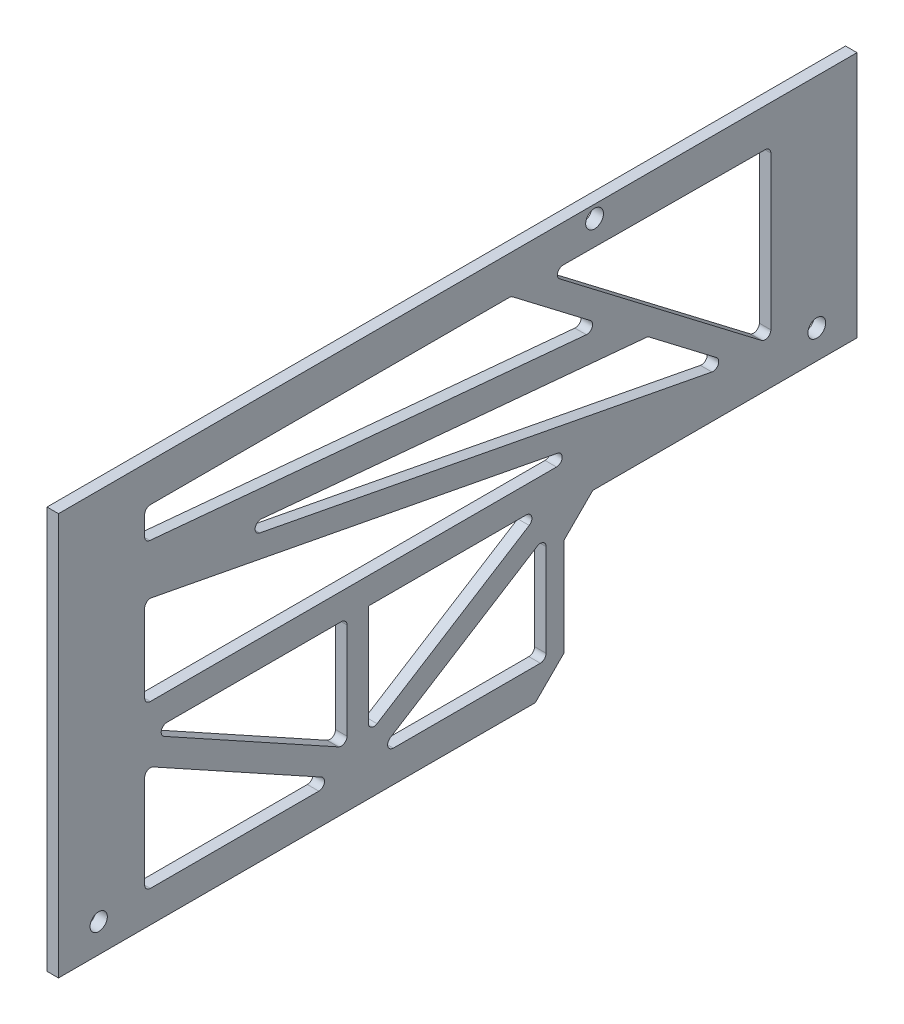
SolidWorks part; units mm, degrees
material "PE 低密度结膜"
ref_plane "前视基准面" through (0, 0, 0) normal (0, 0, 1) x (1, 0, 0)
ref_plane "上视基准面" through (0, 0, 0) normal (0, 1, 0) x (1, 0, 0)
ref_plane "右视基准面" through (0, 0, 0) normal (1, 0, 0) x (0, 0, -1)
sketch "草图2" plane through (0, 0, 0) normal (1, 0, 0) x (0, 0, -1)
  line L1 (0, 0) -> (139, 0)
  line L2 (0, 0) -> (0, 110)
  line L3 (0, 110) -> (139, 110)
  line L4 (139, 0) -> (139, 110)
  line L5 (139, 0) -> (88, 0)
  line L6 (139, 0) -> (139, 27)
  line L7 (139, 27) -> (88, 27)
  line L8 (88, 0) -> (88, 27)
  dimension "D1" = 139
  dimension "D2" = 110
  dimension "D3" = 51
  dimension "D4" = 27
extrude "凸台-拉伸1" add sketch "草图2" along normal blind 2 contours L1 L8 L7 L4 L3 L2 region at (0, 59.1073, -65.1452)
sketch "草图3" plane through (0, 110, 0) normal (0, 1, 0) x (1, 0, 0)
  line L1 (0, 139) -> (2, 139)
  line L2 (0, 139) -> (0, 0)
  line L3 (0, 0) -> (2, 0)
  line L4 (2, 139) -> (2, 0)
extrude "切除-拉伸1" cut sketch "草图3" against normal blind 40
sketch "草图4" plane through (-10, 0, 0) normal (-1, 0, 0) x (0, 0, 1)
  circle A0 centre (-7, 5) radius 1.5
  circle A1 centre (-132, 30) radius 1.5
  circle A3 centre (-93.3167, 67.822) radius 1.55
  dimension "D1" = 3.1
extrude "切除-拉伸3" cut sketch "草图4" against normal blind 14
sketch "草图5" plane through (2, 0, 0) normal (1, 0, 0) x (0, 0, -1)
  circle A0 centre (132, 30) radius 1.5
extrude "凸台-拉伸2" add sketch "草图5" against normal up to surface (2 mm away) up to face at (0, 5, -8.5)
sketch "草图6" plane through (2, 0, 0) normal (1, 0, 0) x (0, 0, -1)
  line L1 (139, 27) -> (132, 27)
  line L2 (139, 27) -> (139, 32)
  line L3 (139, 32) -> (132, 32)
  line L4 (132, 27) -> (132, 32)
  circle A0 centre (132, 32) radius 1.55
  dimension "D3" = 3.1
  dimension "D1" = 5
  dimension "D2" = 7
extrude "切除-拉伸4" cut sketch "草图6" against normal blind 10 contours L3 A0 L4 | L4 A0 L3 region at (2, 32.2193, -131.7807) region at (2, 31.3422, -132.6578)
chamfer "Chamfer1" distance 5 angle 45 2 edges at (1, 0, -88) (1, 27, -88)
sketch "Sketch1" plane through (0, 0, 0) normal (-1, 0, 0) x (0, 0, 1)
  line L0 (-93.3991, 57.0699) -> (-124, 33.6882)
  line L1 (-124, 33.6882) -> (-124, 54.2625)
  line L3 (-102.609, 45.3791) -> (-117.9095, 33.6882)
  line L4 (-117.9095, 33.6882) -> (-15, 53.4166)
  line L5 (-15, 53.4166) -> (-102.609, 45.3791)
  line L6 (-15, 49.4486) -> (-15, 33.6882)
  line L7 (-15, 33.6882) -> (-97.2112, 33.6882)
  line L8 (-97.2112, 33.6882) -> (-15, 49.4486)
  line L9 (-15, 29.1023) -> (-50.2247, 29.1023)
  line L10 (-50.2247, 29.1023) -> (-50.2247, 9.6509)
  line L11 (-50.2247, 9.6509) -> (-15, 29.1023)
  line L12 (-15, 24.3925) -> (-15, 5.511)
  line L13 (-15, 5.511) -> (-49.1928, 5.511)
  line L14 (-49.1928, 5.511) -> (-15, 24.3925)
  line L15 (-53.9219, 29.1023) -> (-53.9219, 9.6509)
  line L16 (-53.9219, 9.6509) -> (-84.8796, 29.1023)
  line L17 (-84.8796, 29.1023) -> (-53.9219, 29.1023)
  line L18 (-84.8796, 24.3925) -> (-54.8288, 5.511)
  line L19 (-54.8288, 5.511) -> (-84.8796, 5.511)
  line L20 (-84.8796, 5.511) -> (-84.8796, 24.3925)
  line L21 (-95.3369, 50.7176) -> (-15, 58.0879)
  line L22 (-95.3369, 50.7176) -> (-78.7954, 63.3567)
  line L24 (-78.7954, 63.3567) -> (-15, 63.3567)
  line L25 (-15, 63.3567) -> (-15, 58.0879)
  line L26 (-124, 54.2625) -> (-124, 63.3567)
  line L27 (-93.3991, 57.0699) -> (-84.8796, 63.5796)
  line L28 (-84.8796, 63.5796) -> (-124, 63.3567)
extrude "Cut-Extrude1" cut sketch "Sketch1" against normal blind 10
fillet "Fillet1" radius 1 24 edges at (1, 33.6882, -124) (1, 33.6882, -97.2112) (1, 24.3925, -84.8796) (1, 5.511, -54.8288) (1, 9.6509, -53.9219) (1, 9.6509, -50.2247) (1, 24.3925, -15) (1, 5.511, -15) (1, 29.1023, -15) (1, 33.6882, -15) (1, 49.4486, -15) (1, 53.4166, -15) (1, 50.7176, -95.3369) (1, 33.6882, -117.9095) (1, 5.511, -49.1928) (1, 5.511, -84.8796) (1, 29.1023, -50.2247) (1, 29.1023, -84.8796) (1, 45.3791, -102.609) (1, 63.3567, -78.7954) (1, 58.0879, -15) (1, 63.3567, -15) (1, 63.3567, -124) (1, 63.5796, -84.8796)
